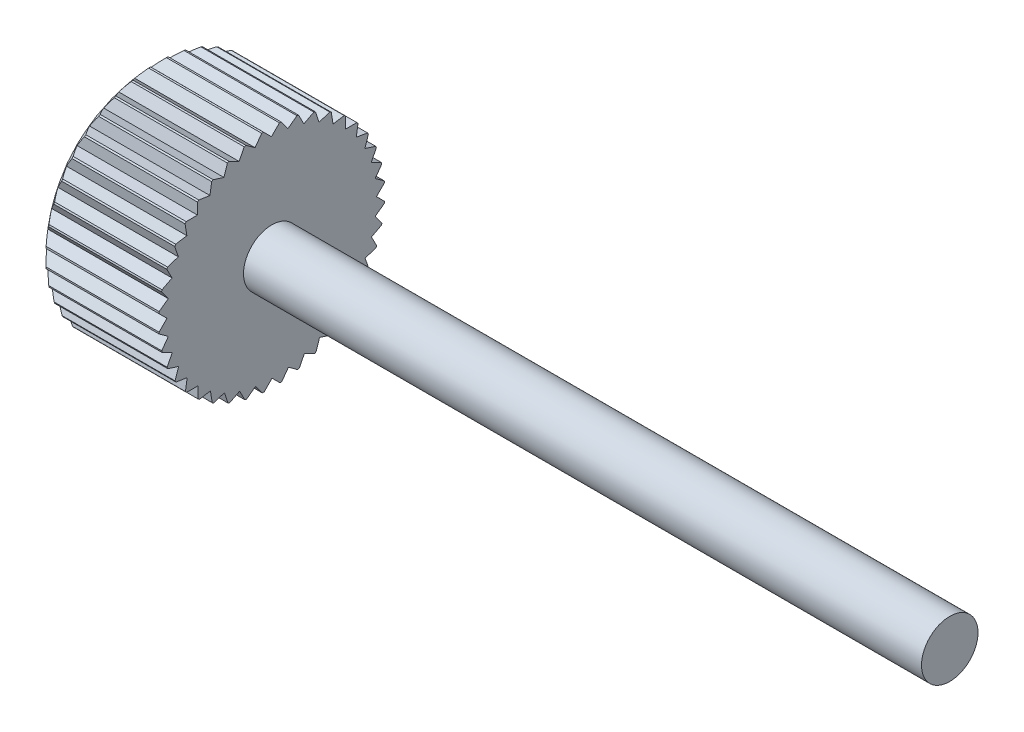
SolidWorks part; units mm, degrees
ref_plane "Front Plane" through (0, 0, 0) normal (0, 0, 1) x (1, 0, 0)
ref_plane "Top Plane" through (0, 0, 0) normal (0, 1, 0) x (1, 0, 0)
ref_plane "Right Plane" through (0, 0, 0) normal (1, 0, 0) x (0, 0, -1)
sketch "Sketch1" plane through (0, 0, 0) normal (1, 0, 0) x (0, 0, -1)
  circle A0 centre (0, 0) radius 2
  dimension "D1" = 4
extrude "Boss-Extrude1" add sketch "Sketch1" along normal blind 2
sketch "Sketch2" plane through (2, 0, 0) normal (1, 0, 0) x (0, 0, -1)
  circle A0 centre (0, 0) radius 0.5
  dimension "D1" = 1
extrude "Boss-Extrude2" add sketch "Sketch2" along normal blind 12
dome "Dome1" faces to dome 1 distance 0.8 reverse direction no elliptical dome no face at (0, 0, -2) parameters "D1"=0.8
sketch "Sketch3" plane through (2, 0, 0) normal (1, 0, 0) x (0, 0, -1)
  line L0 (-0.005, 1.8536) -> (0.136, 1.9954)
  line L1 (-0.005, 1.8536) -> (-0.1468, 1.9946)
  circle A1 centre (0, 0) radius 2
  arc A2 (0.136, 1.9954) -> (-0.1468, 1.9946) centre (0, 0) ccw
  dimension "D2" = 0.2
  dimension "D3" = 0.2
  dimension "D4" = 90
  dimension "D1" = 0
extrude "Cut-Extrude1" cut sketch "Sketch3" against normal through all
pattern_circular "CirPattern1" count 40 over 360 about axis through (2, 0, 0) along (1, 0, 0) of "Cut-Extrude1"
